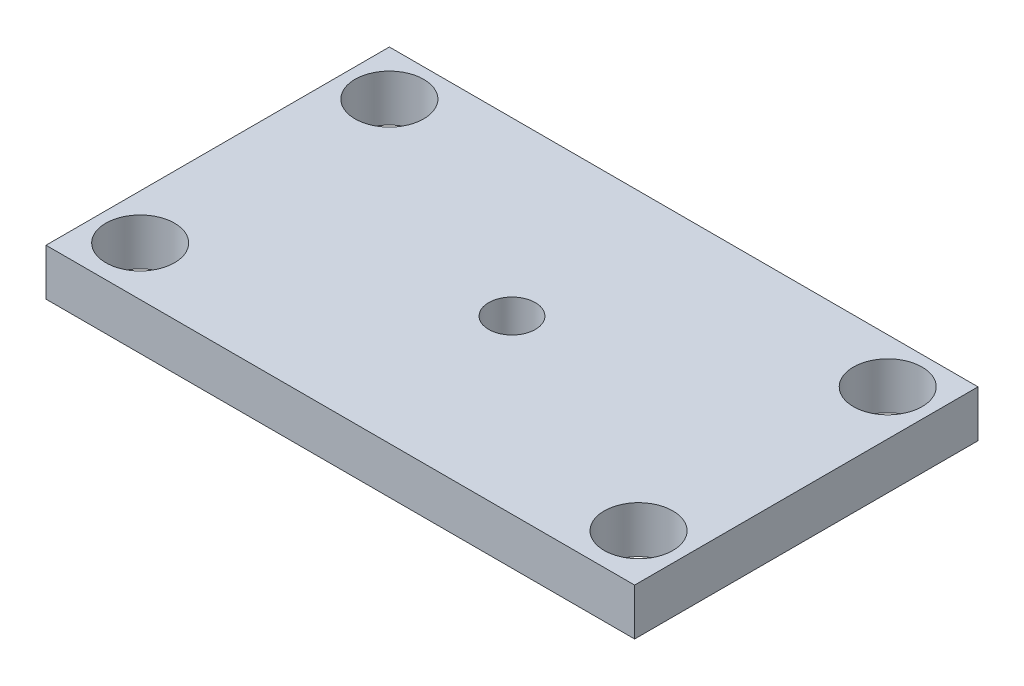
SolidWorks part; units mm, degrees
ref_plane "Front Plane" through (0, 0, 0) normal (0, 0, 1) x (1, 0, 0)
ref_plane "Top Plane" through (0, 0, 0) normal (0, 1, 0) x (1, 0, 0)
ref_plane "Right Plane" through (0, 0, 0) normal (1, 0, 0) x (0, 0, -1)
sketch "Sketch1" plane through (0, 0, 0) normal (0, 1, 0) x (1, 0, 0)
  line L0 (4.6, 30.4) -> (0, 30.4) construction
  line L1 (0, 0) -> (60, 0)
  line L2 (0, 0) -> (0, 35)
  line L3 (0, 35) -> (60, 35)
  line L4 (60, 0) -> (60, 35)
  line L5 (4.6, 30.4) -> (55.4, 30.4) construction
  line L6 (4.6, 30.4) -> (4.6, 5) construction
  line L7 (4.6, 5) -> (55.4, 5) construction
  line L8 (55.4, 30.4) -> (55.4, 5) construction
  line L9 (4.6, 30.4) -> (4.6, 35) construction
  circle A0 centre (4.6, 30.4) radius 3.5
  circle A1 centre (55.4, 30.4) radius 3.5
  circle A2 centre (4.6, 5) radius 3.5
  circle A3 centre (55.4, 5) radius 3.5
  circle A4 centre (30, 17.5) radius 2.375
  point P13 (30, 30.4)
  point P14 (30, 35)
  point P20 (60, 17.5)
  dimension "D5" = 7
  dimension "D6" = 4.75
  dimension "D1" = 60
  dimension "D2" = 35
  dimension "D3" = 50.8
  dimension "D4" = 25.4
extrude "Boss-Extrude1" add sketch "Sketch1" along normal blind 4.7625
